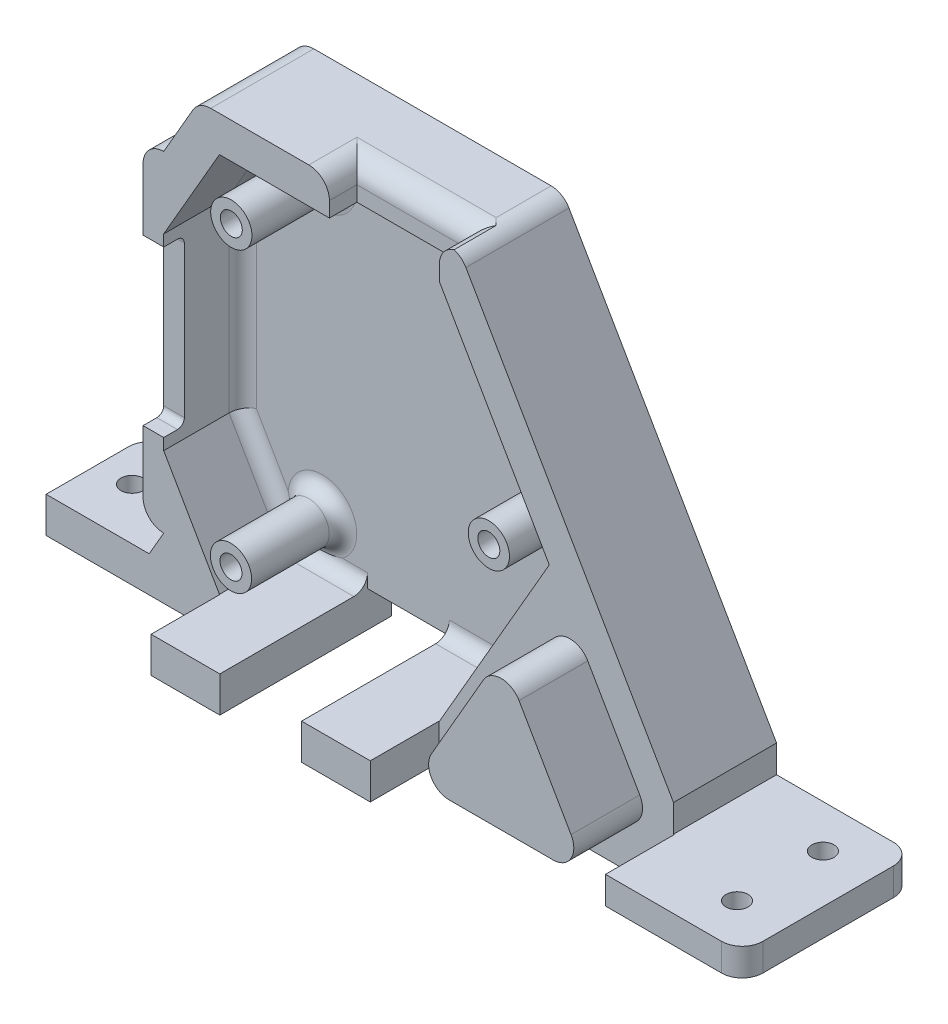
SolidWorks part; units mm, degrees
ref_plane "Plan de face" through (0, 0, 0) normal (0, 0, 1) x (1, 0, 0)
ref_plane "Plan de dessus" through (0, 0, 0) normal (0, 1, 0) x (1, 0, 0)
ref_plane "Plan de droite" through (0, 0, 0) normal (1, 0, 0) x (0, 0, -1)
sketch "Esquisse1" plane through (0, 0, 0) normal (0, 0, 1) x (1, 0, 0)
  line L1 (38, 0) -> (19, 32.909)
  line L2 (19, 32.909) -> (-19, 32.909)
  line L3 (-19, 32.909) -> (-38, 0)
  line L4 (-38, 0) -> (-19, -32.909)
  line L5 (-19, -32.909) -> (19, -32.909)
  line L6 (19, -32.909) -> (38, 0)
  circle A0 centre (0, 0) radius 32.909 construction
  dimension "D1" = 38
extrude "Boss.-Extru.1" add sketch "Esquisse1" along normal blind 15
sketch "Esquisse2" plane through (0, 0, 15) normal (0, 0, 1) x (1, 0, 0)
  line L1 (32, 0) -> (16, 27.7128)
  line L2 (16, 27.7128) -> (-16, 27.7128)
  line L3 (-16, 27.7128) -> (-32, 0)
  line L4 (-32, 0) -> (-16, -27.7128)
  line L5 (-16, -27.7128) -> (16, -27.7128)
  line L6 (16, -27.7128) -> (32, 0)
  circle A0 centre (0, 0) radius 27.7128 construction
  dimension "D1" = 32
extrude "Enlèv. mat.-Extru.1" cut sketch "Esquisse2" against normal blind 11.5
sketch "Esquisse3" plane through (0, 0, 3.5) normal (0, 0, 1) x (1, 0, 0)
  line L1 (-12.5234, -21.6371) -> (25, -0.027) construction
  line L2 (25, -0.027) -> (-12.4766, 21.6641) construction
  line L3 (-12.4766, 21.6641) -> (-12.5234, -21.6371) construction
  circle A0 centre (0, 0) radius 12.5 construction
  circle A1 centre (-12.5234, -21.6371) radius 3
  circle A2 centre (-12.4766, 21.6641) radius 3
  circle A3 centre (25, -0.027) radius 3
  point P9 (-12.4766, -21.6371)
  dimension "D2" = 6
  dimension "D3" = 6
  dimension "D4" = 6
  dimension "D1" = 25
extrude "Boss.-Extru.2" add sketch "Esquisse3" along normal blind 13.3
hole_wizard "Chambrage pour vis à tête ronde bombée M31" positions "Esquisse4" profile "Esquisse5" counterbore size "M3" standard "Ansi Metric" end condition through all
sketch "Esquisse4" plane through (0, 0, 0) normal (0, 0, -1) x (-1, 0, 0)
  point P0 (12.4766, 21.6641)
  point P3 (12.5234, -21.6371)
  point P6 (-25, -0.027)
sketch "Esquisse5" plane through (-12.4766, 21.6641, 0) normal (1, 0, 0) x (0, 1, 0)
  line L0 (0, 0) -> (0, 16.8)
  line L1 (0, 16.8) -> (1.6, 16.8)
  line L3 (1.6, 16.8) -> (1.6, 2.4)
  line L4 (1.6, 2.4) -> (3.5, 2.4)
  line L5 (3.5, 2.4) -> (3.5, 0)
  line L7 (3.5, 0) -> (0, 0)
  line L11 (0, -6.35) -> (0, 107.95) construction
  dimension "Diamètre du perçage jusqu'au prochain" = 3.2
  dimension "Profondeur du perçage jusqu'au prochain" = 16.8
  dimension "Diamètre du chambrage" = 7
  dimension "Profondeur du chambrage" = 2.4
sketch "Esquisse6" plane through (0, 0, 3.5) normal (0, 0, 1) x (1, 0, 0)
  line L20 (-27.1132, 5) -> (-15, 25.9808) construction
  line L21 (-15, -25.9808) -> (-27.1132, -5) construction
  line L22 (15, -25.9808) -> (-15, -25.9808) construction
  line L23 (30, 0) -> (15, -25.9808) construction
  line L24 (15, 25.9808) -> (30, 0) construction
  line L25 (-15, 25.9808) -> (15, 25.9808) construction
  line L26 (-27.1132, -5) -> (-27.1132, 5) construction
  line L27 (-24.1132, 32.909) -> (-24.1132, -32.909)
  line L28 (-50.1969, -32.909) -> (-24.1132, -32.909)
  line L29 (-50.1969, 32.909) -> (-50.1969, -32.909)
  line L30 (-50.1969, 32.909) -> (-24.1132, 32.909)
  dimension "D1" = 3
extrude "Enlèv. mat.-Extru.2" cut sketch "Esquisse6" against normal through all both and the other way through all
sketch "Esquisse7" plane through (0, 0, 15) normal (0, 0, 1) x (1, 0, 0)
  line L0 (38, 0) -> (19, -32.909)
  line L1 (19, -32.909) -> (50.0718, -32.909)
  line L4 (50.0718, -20.909) -> (38, 0)
  line L5 (38, 0) -> (19, 32.909) construction
  line L7 (50.0718, -20.909) -> (50.0718, -24.909)
  line L8 (50.0718, -24.909) -> (70.073, -24.909)
  line L9 (70.073, -28.909) -> (50.0718, -28.909)
  line L10 (50.0718, -28.909) -> (50.0718, -32.909)
  line L11 (70.073, -28.909) -> (70.073, -24.909)
  dimension "D1" = 4
  dimension "D2" = 4
  dimension "D3" = 4
  dimension "D4" = 20.0013
extrude "Boss.-Extru.3" add sketch "Esquisse7" against normal up to surface (15 mm away) up to face at (-15.9766, 21.6641, 0)
sketch "Esquisse8" plane through (0, 0, 15) normal (0, 0, 1) x (1, 0, 0)
  line L0 (-16, -27.7128) -> (16, -27.7128) construction
  line L1 (-15.95, -27.7128) -> (-5.95, -27.7128)
  line L2 (-15.95, -27.7128) -> (-15.95, -32.909)
  line L3 (-15.95, -32.909) -> (-5.95, -32.909)
  line L4 (-5.95, -27.7128) -> (-5.95, -32.909)
  line L6 (-19, -32.909) -> (50.0718, -32.909) construction
  line L7 (-16, -27.7128) -> (16, -27.7128) construction
  line L8 (15.95, -27.7128) -> (5.95, -27.7128)
  line L9 (15.95, -27.7128) -> (15.95, -32.909)
  line L10 (15.95, -32.909) -> (5.95, -32.909)
  line L11 (5.95, -27.7128) -> (5.95, -32.909)
  line L13 (70.073, -28.909) -> (50.173, -28.909)
  line L14 (70.073, -28.909) -> (70.073, -24.909)
  line L15 (70.073, -24.909) -> (50.173, -24.909)
  line L16 (50.173, -28.909) -> (50.173, -24.909)
  line L17 (70.073, -28.909) -> (70.073, -24.909) construction
  line L18 (70.073, -24.909) -> (50.0718, -24.909) construction
  point P23 (73.5359, -33.8163)
  dimension "D1" = 0.05
  dimension "D2" = 10
  dimension "D3" = 0.05
  dimension "D4" = 10
  dimension "D5" = 4
  dimension "D7" = 19.9
extrude "Boss.-Extru.4" add sketch "Esquisse8" along normal blind 10
sketch "Esquisse12" plane through (0, 0, 15) normal (0, 0, 1) x (1, 0, 0)
  line L0 (50.0718, -20.909) -> (19, 32.909) construction
  line L1 (47.7624, -26.909) -> (35, -4.8038)
  line L2 (35, -4.8038) -> (22.2376, -26.909)
  line L3 (22.2376, -26.909) -> (47.7624, -26.909)
  line L4 (16, -27.7128) -> (32, 0) construction
  line L6 (15.95, -32.909) -> (50.0718, -32.909) construction
  circle A0 centre (35, -19.5406) radius 7.3684 construction
  dimension "D1" = 6
  dimension "5" = 5
  dimension "D2" = 5
extrude "Boss.-Extru.5" add sketch "Esquisse12" along normal blind 10
sketch "Esquisse13" plane through (0, 0, 15) normal (0, 0, 1) x (1, 0, 0)
  line L1 (-5.95, -32.909) -> (5.95, -32.909)
  line L2 (-5.95, -32.909) -> (-5.95, -27.7128)
  line L3 (-5.95, -27.7128) -> (5.95, -27.7128)
  line L4 (5.95, -32.909) -> (5.95, -27.7128)
extrude "Enlèv. mat.-Extru.3" cut sketch "Esquisse13" against normal up to surface (15 mm away) up to face at (-15.9766, 21.6641, 0)
sketch "Esquisse14" plane through (0, 0, 15) normal (0, 0, 1) x (1, 0, 0)
  line L0 (19, 32.909) -> (-19, 32.909) construction
  line L1 (0, 27.7128) -> (16, 27.7128)
  line L2 (0, 27.7128) -> (0, 32.909)
  line L3 (0, 32.909) -> (16, 32.909)
  line L4 (16, 27.7128) -> (16, 32.909)
  point P7 (0, 0)
  point P8 (16, 27.7128)
  dimension "D1" = 16
extrude "Enlèv. mat.-Extru.4" cut sketch "Esquisse14" against normal blind 4
sketch "Esquisse15" plane through (0, 0, 15) normal (0, 0, 1) x (1, 0, 0)
  line L0 (-24.1132, -24.0526) -> (-26.2243, -27.709)
  line L1 (-26.2243, -27.709) -> (-41.2243, -27.709)
  line L2 (-41.2243, -27.709) -> (-41.2243, -32.909)
  line L3 (-41.2243, -32.909) -> (-19, -32.909)
  line L4 (-19, -32.909) -> (-24.1132, -24.0526)
  dimension "D1" = 15
  dimension "D2" = 5.2
  dimension "D3" = 60
extrude "Boss.-Extru.6" add sketch "Esquisse15" against normal up to surface (15 mm away) up to face at (-15.9766, 21.6641, 0)
sketch "Esquisse16" plane through (0, -27.709, 0) normal (0, 1, 0) x (1, 0, 0)
  line L0 (-41.2243, -7.5) -> (-36.2243, -7.5) construction
  line L1 (-41.2243, 0) -> (-41.2243, -15) construction
  dimension "D1" = 5
hole_wizard "Dégagement M32" positions "Esquisse17" profile "Esquisse18" hole size "M3" standard "Ansi Metric" end condition through all
sketch "Esquisse17" plane through (0, -27.709, 0) normal (0, 1, 0) x (1, 0, 0)
  point P0 (-36.2243, -7.5)
sketch "Esquisse18" plane through (-36.2243, -27.709, 7.5) normal (1, 0, 0) x (0, 0, 1)
  line L0 (0, 0) -> (0, 5.2)
  line L1 (0, 5.2) -> (1.6, 5.2)
  line L2 (1.6, 5.2) -> (1.6, 0)
  line L5 (1.6, 0) -> (0, 0)
  line L11 (0, -6.35) -> (0, 107.95) construction
  dimension "Diamètre du perçage jusqu'au prochain" = 3.2
  dimension "Profondeur du perçage jusqu'au prochain" = 5.2
sketch "Esquisse19" plane through (0, -24.909, 0) normal (0, 1, 0) x (1, 0, 0)
  line L0 (63.073, 0) -> (63.073, -25) construction
  line L1 (50.0718, 0) -> (70.073, 0) construction
  line L2 (70.073, -25) -> (50.173, -25) construction
  line L3 (70.073, 0) -> (70.073, -25) construction
  point P8 (63.073, -6.25)
  point P9 (63.073, -18.75)
  dimension "D1" = 7
  dimension "D2" = 6.25
  dimension "D3" = 6.25
hole_wizard "Dégagement M33" positions "Esquisse20" profile "Esquisse21" hole size "M3" standard "Ansi Metric" end condition through all
sketch "Esquisse20" plane through (0, -24.909, 0) normal (0, 1, 0) x (1, 0, 0)
  point P0 (63.073, -6.25)
  point P3 (63.073, -18.75)
sketch "Esquisse21" plane through (63.073, -24.909, 6.25) normal (1, 0, 0) x (0, 0, 1)
  line L0 (0, 0) -> (0, 8)
  line L1 (0, 8) -> (1.6, 8)
  line L2 (1.6, 8) -> (1.6, 0)
  line L5 (1.6, 0) -> (0, 0)
  line L11 (0, -6.35) -> (0, 107.95) construction
  dimension "Diamètre du perçage jusqu'au prochain" = 3.2
  dimension "Profondeur du perçage jusqu'au prochain" = 8
sketch "Esquisse22" plane through (-24.1132, 0, 0) normal (-1, 0, 0) x (0, 0, 1)
  line L2 (15, -12) -> (12, -12)
  line L3 (12, -12) -> (12, 12)
  line L4 (12, 12) -> (15, 12)
  line L5 (15, 12) -> (15, 24.0526)
  line L7 (15, 24.0526) -> (0, 24.0526)
  line L8 (0, 24.0526) -> (0, -24.0526)
  line L9 (0, -24.0526) -> (15, -24.0526)
  line L11 (15, -12) -> (15, -24.0526)
  line L12 (15, -24.0526) -> (15, -13.6603) construction
  line L13 (0, -24.0526) -> (0, 24.0526) construction
  line L14 (15, -24.0526) -> (0, -24.0526) construction
  line L15 (0, 24.0526) -> (15, 24.0526) construction
  line L16 (15, 0) -> (15, 27.7128) construction
  dimension "D1" = 12
  dimension "D2" = 12
  dimension "D3" = 3
extrude "Boss.-Extru.7" add sketch "Esquisse22" along normal blind 3
fillet "Congé1" radius 3 13 edges at (47.7624, -26.909, 20) (22.2376, -26.909, 20) (35, -4.8038, 20) (-19, 32.909, 7.5) (19, 32.909, 7.5) (70.073, -26.909, 0) (70.073, -26.909, 25) (16, 32.909, 13) (8, 32.909, 11) (0, 32.909, 13) (-41.2243, -30.309, 0) (-27.1132, 24.0526, 7.5) (-27.1132, -24.0526, 7.5)
fillet "Congé2" radius 1 2 edges at (-25.6132, 12, 12) (-25.6132, -12, 12)
fillet "Congé3" radius 2 10 edges at (-20.0566, -20.6865, 3.5) (28, -0.027, 3.5) (-9.4766, 21.6641, 3.5) (-9.5234, -21.6371, 3.5) (-10.975, -27.7128, 3.5) (24, -13.8564, 3.5) (24, 13.8564, 3.5) (0, 27.7128, 3.5) (-20.0566, 20.6865, 3.5) (-24.1132, 0, 3.5)
